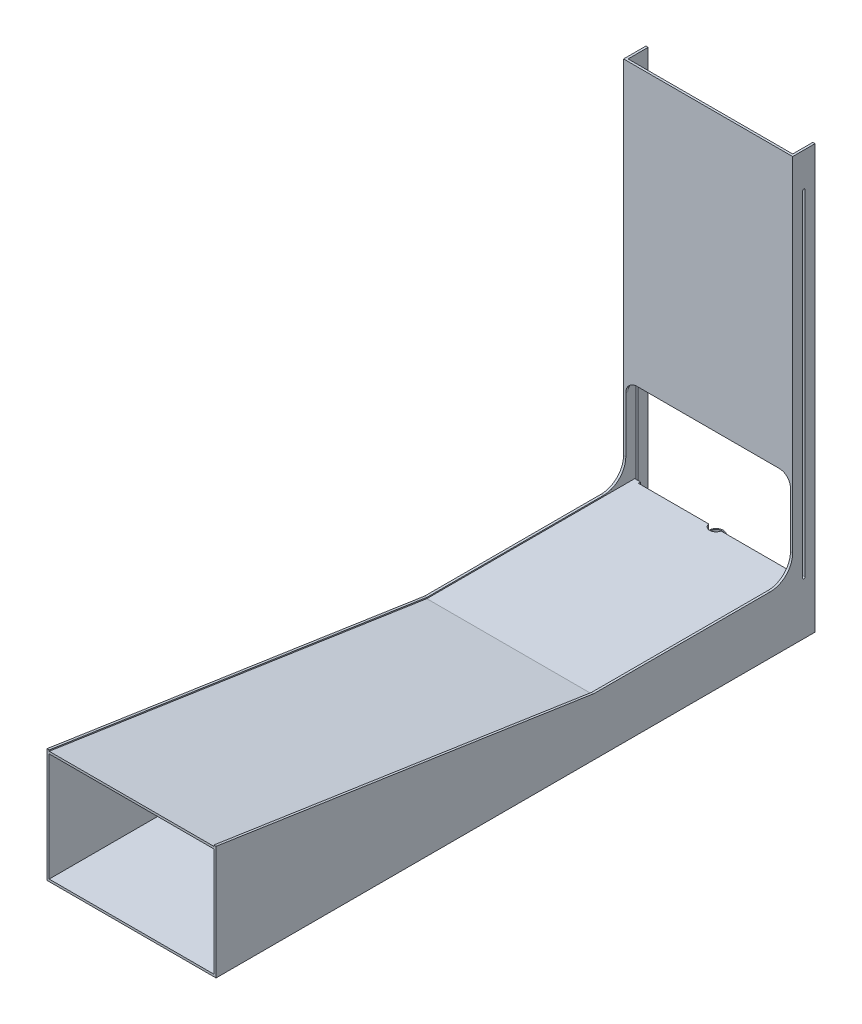
SolidWorks part; units mm, degrees
material "AISI 4340 Steel, annealed"
ref_plane "Front Plane" through (0, 0, 0) normal (0, 0, 1) x (1, 0, 0)
ref_plane "Top Plane" through (0, 0, 0) normal (0, 1, 0) x (1, 0, 0)
ref_plane "Right Plane" through (0, 0, 0) normal (1, 0, 0) x (0, 0, -1)
ref_plane "Right side of elevator platform" through (368, 0, 0) normal (1, 0, 0) x (0, 0, -1)
sketch "Sketch2" plane through (368, 0, 0) normal (1, 0, 0) x (0, 0, -1)
  line L0 (50, 236.5) -> (50, 1736.5) construction
  line L1 (45, 236.5) -> (45, 1736.5)
  line L2 (55, 236.5) -> (55, 1736.5)
  line L4 (0, 0) -> (100, 0)
  line L5 (0, 0) -> (0, 1800)
  line L6 (0, 1800) -> (100, 1800)
  line L7 (100, 0) -> (100, 1800)
  arc A0 (45, 236.5) -> (55, 236.5) centre (50, 236.5) ccw
  arc A1 (55, 1736.5) -> (45, 1736.5) centre (50, 1736.5) ccw
  point P2 (50, 986.5)
  dimension "D6" = 5
  dimension "D1" = 1800
  dimension "D2" = 100
  dimension "D3" = 50
  dimension "D4" = 236.5
  dimension "D5" = 63.5
extrude "Right side guide" add sketch "Sketch2" along normal blind 10
sketch "Sketch3" plane through (368, 0, 0) normal (-1, 0, 0) x (0, 0, 1)
  line L0 (0, 1800) -> (0, 0) construction
  line L1 (-100, 0) -> (0, 0)
  line L2 (-100, 0) -> (-100, 10)
  line L3 (-100, 10) -> (0, 10)
  line L4 (0, 0) -> (0, 10)
  dimension "D1" = 10
extrude "Bottom connection" add sketch "Sketch3" along normal blind 736
sketch "Sketch4" plane through (-368, 0, 0) normal (-1, 0, 0) x (0, 0, 1)
  line L0 (-55, 236.5) -> (-55, 1736.5) construction
  line L1 (-45, 1736.5) -> (-45, 236.5) construction
  line L2 (-55, 236.5) -> (-55, 1736.5)
  line L3 (-45, 1736.5) -> (-45, 236.5)
  line L4 (-100, 10) -> (0, 10)
  line L5 (0, 10) -> (0, 1800)
  line L6 (0, 1800) -> (-100, 1800)
  line L7 (-100, 1800) -> (-100, 10)
  line L9 (0, 10) -> (0, 1800)
  line L10 (0, 1800) -> (-100, 1800)
  line L11 (-100, 1800) -> (-100, 10)
  line L16 (-100, 10) -> (-100, 0)
  line L17 (-100, 0) -> (0, 0)
  line L18 (0, 0) -> (0, 10)
  line L19 (0, 10) -> (-100, 10)
  line L20 (-100, 10) -> (-100, 0)
  line L21 (-100, 0) -> (0, 0)
  line L22 (0, 0) -> (0, 10)
  arc A0 (-45, 1736.5) -> (-55, 1736.5) centre (-50, 1736.5) ccw construction
  arc A1 (-55, 236.5) -> (-45, 236.5) centre (-50, 236.5) ccw construction
  arc A2 (-45, 1736.5) -> (-55, 1736.5) centre (-50, 1736.5) ccw
  arc A3 (-55, 236.5) -> (-45, 236.5) centre (-50, 236.5) ccw
  dimension "D1" = 0
  dimension "D2" = 0
extrude "Left side guide" add sketch "Sketch4" along normal blind 10
sketch "Sketch5" plane through (0, 0, 0) normal (0, 0, 1) x (1, 0, 0)
  line L0 (-368, 10) -> (-368, 1800) construction
  line L1 (-368, 1800) -> (368, 1800)
  line L2 (-368, 1800) -> (-368, 653.8)
  line L3 (-368, 653.8) -> (368, 653.8)
  line L4 (368, 1800) -> (368, 653.8)
  line L5 (368, 1800) -> (368, 10) construction
  line L6 (378, 1800) -> (368, 1800) construction
  line L7 (-368, 10) -> (368, 10) construction
  dimension "D1" = 643.8
extrude "Structural webbing extrude" add sketch "Sketch5" against normal blind 10
sketch "Sketch6" plane through (0, 0, 0) normal (0, 0, 1) x (1, 0, 0)
  line L0 (-378, 251.5) -> (-378, 0)
  line L1 (-378, 0) -> (-378, 1800) construction
  line L2 (-378, 0) -> (378, 0)
  line L3 (378, 0) -> (378, 251.5)
  line L4 (378, 1800) -> (378, 0) construction
  line L5 (378, 251.5) -> (368, 251.5)
  line L6 (368, 653.8) -> (368, 10) construction
  line L7 (368, 251.5) -> (368, 10)
  line L8 (368, 10) -> (-368, 10)
  line L9 (-368, 10) -> (-368, 251.5)
  line L10 (-368, 10) -> (-368, 653.8) construction
  line L11 (-368, 251.5) -> (-378, 251.5)
  dimension "D1" = 241.5
extrude "Input roller holder extrude" add sketch "Sketch6" along normal blind 452.52
sketch "Sketch7" plane through (368, 0, 0) normal (-1, 0, 0) x (0, 0, 1)
  line L0 (0, 653.8) -> (0, 251.5) construction
  line L1 (452.52, 251.5) -> (-40, 251.5)
  line L2 (452.52, 251.5) -> (452.52, 241.5)
  line L3 (452.52, 241.5) -> (-40, 241.5)
  line L4 (-40, 251.5) -> (-40, 241.5)
  dimension "D1" = 40
  dimension "D2" = 10
extrude "Input roller platform" add sketch "Sketch7" along normal up to next
sketch "Sketch8" plane through (0, 251.5, 0) normal (0, 1, 0) x (1, 0, 0)
  line L1 (-378, -452.52) -> (-368, -452.52)
  line L2 (-378, -452.52) -> (-378, 0)
  line L3 (-378, 0) -> (-368, 0)
  line L4 (-368, -452.52) -> (-368, 0)
  line L5 (368, 0) -> (378, 0)
  line L6 (368, 0) -> (368, -452.52)
  line L7 (368, -452.52) -> (378, -452.52)
  line L8 (378, 0) -> (378, -452.52)
extrude "Siding outline" add sketch "Sketch8" along normal blind 5
sketch "Sketch9" plane through (0, 1800, 0) normal (0, 1, 0) x (1, 0, 0)
  line L8 (368, 100) -> (368, 10)
  line L9 (368, 10) -> (-368, 10)
  line L10 (-368, 10) -> (-368, 100)
  line L11 (-368, 100) -> (-378, 100)
  line L12 (-378, 100) -> (-378, 0)
  line L13 (-378, 0) -> (378, 0)
  line L14 (378, 0) -> (378, 100)
  line L15 (378, 100) -> (368, 100)
  line L16 (368, 100) -> (368, 10)
  line L17 (368, 10) -> (-368, 10)
  line L18 (-368, 10) -> (-368, 100)
  line L19 (-368, 100) -> (-378, 100)
  line L20 (-378, 100) -> (-378, 0)
  line L21 (-378, 0) -> (378, 0)
  line L22 (378, 0) -> (378, 100)
  line L23 (378, 100) -> (368, 100)
  dimension "D1" = 0
extrude "Lip to prevent box from falling out" add sketch "Sketch9" along normal blind 91.5
fillet "Vertical section fillets" radius 100 2 edges at (373, 256.5, 0) (-373, 256.5, 0)
fillet "Smaller fillets" radius 50 2 edges at (368, 653.8, -5) (-368, 653.8, -5)
sketch "Sketch11" plane through (0, 0, -40) normal (0, 0, -1) x (-1, 0, 0)
  line L0 (368, 251.5) -> (-368, 251.5) construction
  line L1 (-343, 251.5) -> (343, 251.5)
  line L2 (-343, 251.5) -> (-343, 241.5)
  line L3 (-343, 241.5) -> (343, 241.5)
  line L4 (343, 251.5) -> (343, 241.5)
  line L5 (368, 241.5) -> (-368, 241.5) construction
  line L6 (-368, 251.5) -> (-368, 241.5) construction
  line L7 (368, 251.5) -> (368, 241.5) construction
  dimension "D1" = 25
  dimension "D2" = 25
extrude "Gate spacing cut" cut sketch "Sketch11" against normal blind 10
sketch "Sketch12" plane through (-368, 0, 0) normal (1, 0, 0) x (0, 0, -1)
  line L1 (45, 221.5) -> (40, 221.5)
  line L2 (45, 221.5) -> (45, 10)
  line L3 (45, 10) -> (40, 10)
  line L4 (40, 221.5) -> (40, 10)
  line L5 (100, 1891.5) -> (100, 10) construction
  line L6 (45, 236.5) -> (45, 1736.5) construction
  line L7 (-452.52, 10) -> (100, 10) construction
  line L8 (40, 241.5) -> (-452.52, 241.5) construction
  line L9 (30, 241.5) -> (25, 241.5)
  line L10 (30, 241.5) -> (30, 10)
  line L11 (30, 10) -> (25, 10)
  line L12 (25, 241.5) -> (25, 10)
  dimension "D1" = 60
  dimension "D2" = 20
  dimension "D3" = 5
extrude "Gate guide rails" add sketch "Sketch12" along normal up to next
sketch "Sketch13" plane through (0, 0, -45) normal (0, 0, -1) x (-1, 0, 0)
  line L0 (-368, 221.5) -> (368, 221.5) construction
  line L1 (-328, 221.5) -> (328, 221.5)
  line L2 (-328, 221.5) -> (-328, 10)
  line L3 (-328, 10) -> (328, 10)
  line L4 (328, 221.5) -> (328, 10)
  line L5 (368, 10) -> (-368, 10) construction
  line L6 (-368, 10) -> (-368, 1891.5) construction
  point P8 (0, 221.5)
  dimension "D1" = 40
extrude "Gate rod connection cutout" cut sketch "Sketch13" against normal through all
sketch "Sketch14" plane through (0, 10, 0) normal (0, 1, 0) x (1, 0, 0)
  line L0 (328, 45) -> (-328, 25) construction
  circle A0 centre (0, 35) radius 28
  circle A1 centre (0, 35) radius 33
  point P7 (0, 35)
  dimension "D1" = 56
  dimension "D2" = 5
extrude "Spring cup" add sketch "Sketch14" along normal blind 75
sketch "Sketch15" plane through (0, 85, 0) normal (0, 1, 0) x (1, 0, 0)
  line L0 (368, 30) -> (328, 30) construction
  line L1 (32.619, 30) -> (27.55, 30)
  line L3 (32.619, 40) -> (27.55, 40)
  line L5 (-27.55, 40) -> (-32.619, 40)
  line L6 (-27.55, 30) -> (-32.619, 30)
  circle A0 centre (0, 35) radius 28 construction
  arc A1 (27.55, 40) -> (-27.55, 40) centre (0, 35) ccw
  circle A2 centre (0, 35) radius 33 construction
  arc A3 (32.619, 40) -> (-32.619, 40) centre (0, 35) ccw
  arc A4 (-27.55, 30) -> (27.55, 30) centre (0, 35) ccw
  arc A5 (-32.619, 30) -> (32.619, 30) centre (0, 35) ccw
extrude "Spring container extension" add sketch "Sketch15" along normal up to surface (136.5 mm away) up to face at (0, 221.5, -27.5)
sketch "Sketch16" plane through (0, 221.5, 0) normal (0, 1, 0) x (1, 0, 0)
  circle A0 centre (0, 35) radius 28
  arc A1 (27.55, 40) -> (-27.55, 40) centre (0, 35) ccw construction
extrude "Spring hole (can't insert spring without this)" cut sketch "Sketch16" along normal up to surface (30 mm away) up to face at (0, 251.5, 85.63)
sketch "Sketch17" plane through (0, 221.5, 0) normal (0, 1, 0) x (1, 0, 0)
  line L2 (-26.1534, 25) -> (-31.4484, 25)
  line L3 (31.4484, 25) -> (26.1534, 25)
  line L4 (-26.1534, 25) -> (-31.4484, 25)
  line L5 (31.4484, 25) -> (26.1534, 25)
  arc A2 (-31.4484, 25) -> (31.4484, 25) centre (0, 35) ccw
  arc A3 (-26.1534, 25) -> (26.1534, 25) centre (0, 35) ccw
  arc A4 (-31.4484, 25) -> (31.4484, 25) centre (0, 35) ccw
  arc A5 (-26.1534, 25) -> (26.1534, 25) centre (0, 35) ccw
  dimension "D1" = 0
extrude "Container extension to meet with conveyor plate" add sketch "Sketch17" along normal up to next
fillet "Spring holder fillets" radius 10 4 edges at (0, 10, -68) (-31.4484, 231.5, -25) (31.4484, 231.5, -25) (0, 241.5, -2)
sketch "Sketch18" plane through (0, 0, 452.52) normal (0, 0, 1) x (1, 0, 0)
  line L0 (368, 10) -> (368, 241.5) construction
  line L1 (-368, 241.5) -> (-368, 10) construction
  line L2 (368, 10) -> (368, 241.5)
  line L3 (-368, 241.5) -> (-368, 10)
  line L4 (-368, 241.5) -> (368, 241.5)
  line L5 (368, 10) -> (-368, 10)
  line L8 (378, 0) -> (378, 256.5)
  line L9 (378, 256.5) -> (368, 256.5)
  line L10 (368, 256.5) -> (368, 251.5)
  line L11 (368, 251.5) -> (-368, 251.5)
  line L12 (-368, 251.5) -> (-368, 256.5)
  line L13 (-368, 256.5) -> (-378, 256.5)
  line L14 (-378, 256.5) -> (-378, 0)
  line L15 (-378, 0) -> (378, 0)
  line L16 (378, 0) -> (378, 256.5)
  line L17 (378, 256.5) -> (368, 256.5)
  line L18 (368, 256.5) -> (368, 251.5)
  line L19 (368, 251.5) -> (-368, 251.5)
  line L20 (-368, 251.5) -> (-368, 256.5)
  line L21 (-368, 256.5) -> (-378, 256.5)
  line L22 (-378, 256.5) -> (-378, 0)
  line L23 (-378, 0) -> (378, 0)
  dimension "D1" = 0
extrude "Extension to fit with sorter loop exit stuff" add sketch "Sketch18" along normal blind 437
sketch "Sketch19" plane through (-378, 0, 0) normal (-1, 0, 0) x (0, 0, 1)
  line L0 (889.52, 251.5) -> (2577.86, 504.83)
  line L1 (2577.86, 504.83) -> (2577.86, 494.83)
  line L2 (2577.86, 494.83) -> (889.52, 241.5)
  line L3 (889.52, 256.5) -> (889.52, 0) construction
  line L4 (889.52, 241.5) -> (889.52, 251.5)
  line L6 (889.52, 0) -> (2577.86, 0)
  line L7 (889.52, 0) -> (889.52, 10)
  line L8 (889.52, 10) -> (2577.86, 10)
  line L9 (2577.86, 0) -> (2577.86, 10)
  point P3 (0, 0)
  point P8 (0, 0)
  point P18 (0, 0)
  dimension "D1" = 1688.34
  dimension "D2" = 253.33
extrude "Horizontal plates (extension to output from sorter)" add sketch "Sketch19" against normal up to surface (756 mm away) up to face at (378, 661.6842, 236.9042)
sketch "Sketch20" plane through (0, 0, 0) normal (0, -1, 0) x (1, 0, 0)
  line L0 (0, -544.236) -> (0, 544.236) construction
  line L1 (-378, 2577.86) -> (-368, 2577.86)
  line L2 (-378, 2577.86) -> (-378, 889.52)
  line L3 (-378, 889.52) -> (-368, 889.52)
  line L4 (-368, 2577.86) -> (-368, 889.52)
  line L9 (368, 2577.86) -> (368, 889.52)
  line L10 (378, 889.52) -> (368, 889.52)
  line L11 (378, 2577.86) -> (378, 889.52)
  line L12 (378, 2577.86) -> (368, 2577.86)
  point P5 (0, 0)
  dimension "D1" = 10
extrude "Vertical plates (extension to output from sorter)" add sketch "Sketch20" against normal offset from surface (509.886 mm away) 5 up to face at (0, 335.9433, 1452.3) offset beyond the face yes
